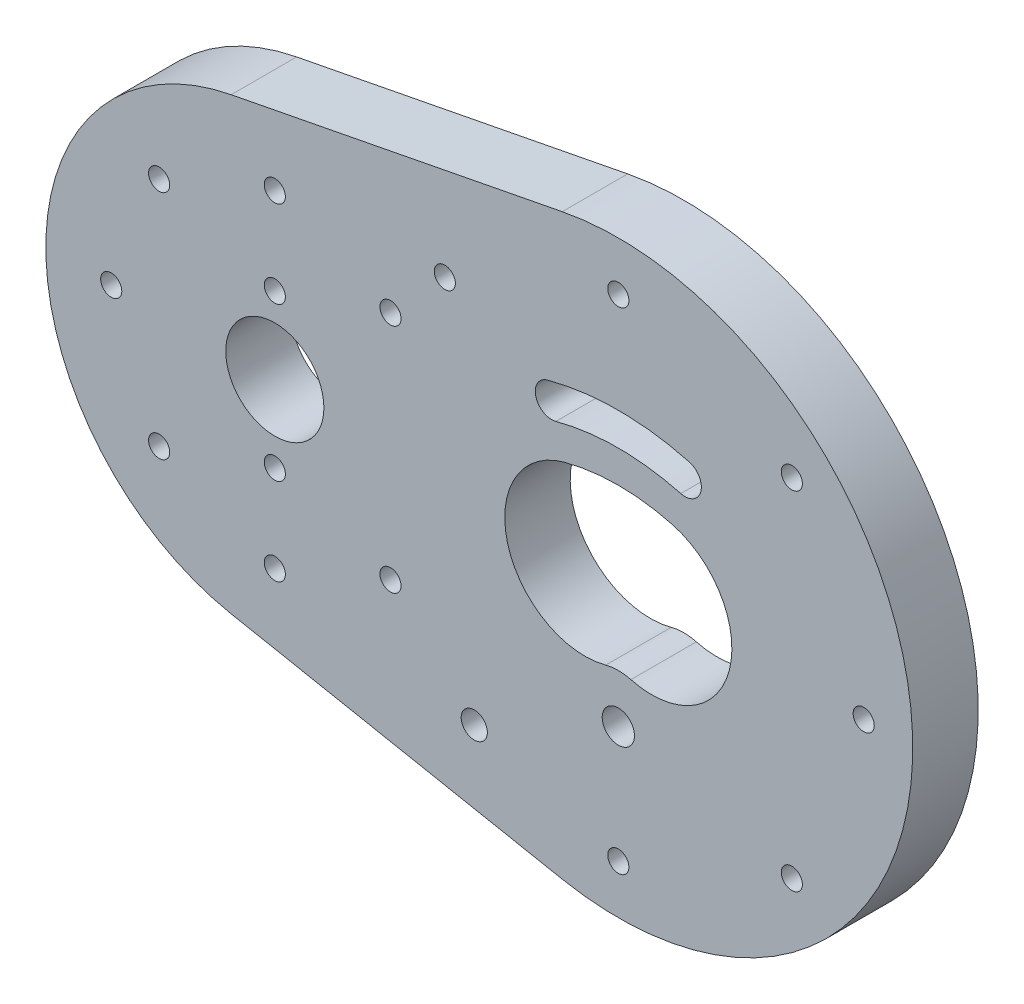
SolidWorks part; units mm, degrees
ref_plane "Front Plane" through (0, 0, 0) normal (0, 0, 1) x (1, 0, 0)
ref_plane "Top Plane" through (0, 0, 0) normal (0, 1, 0) x (1, 0, 0)
ref_plane "Right Plane" through (0, 0, 0) normal (1, 0, 0) x (0, 0, -1)
sketch "Sketch1" plane through (0, 0, 0) normal (0, 0, 1) x (1, 0, 0)
  line L0 (0, 0) -> (0, 36.4546) construction
  line L1 (0, 0) -> (-10.2847, 38.3829) construction
  line L2 (-33.3375, 12.5) -> (0, 12.5) construction
  line L4 (-91.5313, 56.95) -> (35.4687, 56.95)
  line L5 (-91.5313, 56.95) -> (-91.5313, -31.95)
  line L6 (-91.5313, -31.95) -> (35.4687, -31.95)
  line L7 (35.4687, 56.95) -> (35.4687, -31.95)
  line L8 (-91.5313, 56.95) -> (35.4687, -31.95) construction
  line L9 (-91.5313, -31.95) -> (35.4687, 56.95) construction
  arc A0 (5.2502, 19.5939) -> (1.2203, 4.5542) centre (3.2352, 12.0741) cw
  arc A1 (5.2502, 19.5939) -> (-5.2502, 19.5939) centre (0, 0) ccw
  circle A2 centre (0, 12.5) radius 12.5 construction
  circle A3 centre (0, 0) radius 1.5649
  arc A4 (10.8253, 6.25) -> (-10.8253, 6.25) centre (0, 0) ccw construction
  arc A5 (1.2203, 4.5542) -> (-1.2203, 4.5542) centre (0, 0) ccw
  arc A6 (-5.2502, 19.5939) -> (-1.2203, 4.5542) centre (-3.2352, 12.0741) ccw
  circle A7 centre (0, 25) radius 1.5875 construction
  arc A8 (6.8814, 25.6816) -> (-6.8814, 25.6816) centre (0, 0) ccw
  arc A9 (6.0596, 22.6147) -> (-6.0596, 22.6147) centre (0, 0) ccw
  circle A10 centre (0, 0) radius 25 construction
  arc A11 (-6.8814, 25.6816) -> (-6.0596, 22.6147) centre (-6.4705, 24.1481) ccw
  arc A12 (6.8814, 25.6816) -> (6.0596, 22.6147) centre (6.4705, 24.1481) cw
  circle A13 centre (-33.3375, 12.5) radius 4.7625
  circle A14 centre (-33.3375, 12.5) radius 25.4 construction
  point P0 (0, 0)
  point P18 (-28.0313, 12.5)
  dimension "D4" = 25
  dimension "D6" = 50.8
  dimension "D2" = 3.175
  dimension "D3" = 9.525
  dimension "D9" = 7.7851
  dimension "D1" = 15
  dimension "D5" = 33.3375
  dimension "D7" = 88.9
  dimension "D8" = 127
extrude "Boss-Extrude1" add sketch "Sketch1" along normal blind 6.35
sketch "Sketch2" plane through (0, 0, 6.35) normal (0, 0, 1) x (1, 0, 0)
  line L0 (-33.3375, 12.5) -> (43.934, 12.5) construction
  line L1 (0, 0) -> (0, 70.9306) construction
  line L2 (-37.5708, 34.3181) -> (-5.4429, 40.5518)
  line L3 (-37.5708, -9.3181) -> (-5.4429, -15.5518)
  line L5 (-107.0175, 80.3674) -> (70.5021, 80.3674)
  line L6 (-107.0175, 80.3674) -> (-107.0175, -46.3508)
  line L7 (-107.0175, -46.3508) -> (70.5021, -46.3508)
  line L8 (70.5021, 80.3674) -> (70.5021, -46.3508)
  arc A0 (-5.4429, -15.5518) -> (-5.4429, 40.5518) centre (0, 12.5) ccw
  arc A1 (-37.5708, 34.3181) -> (-37.5708, -9.3181) centre (-33.3375, 12.5) ccw
  dimension "D1" = 57.15
  dimension "D2" = 44.45
extrude "Cut-Extrude1" cut sketch "Sketch2" against normal through all
sketch "Sketch4" plane through (0, 0, 6.35) normal (0, 0, 1) x (1, 0, 0)
  line L0 (-33.3375, 12.5) -> (35.849, 12.5) construction
  line L1 (0, 0) -> (0, 48.1146) construction
  circle A0 centre (-33.3375, 12.5) radius 15.875 construction
  circle A1 centre (0, 12.5) radius 23.8125 construction
  circle A2 centre (-33.3375, 28.375) radius 0.635
  circle A3 centre (0, 36.3125) radius 0.635
  circle A4 centre (-22.1122, 23.7253) radius 0.635
  circle A5 centre (-17.4625, 12.5) radius 0.635 [skipped]
  circle A6 centre (-13.9821, -6.8554) radius 1.27
  circle A7 centre (-22.1122, 1.2747) radius 0.635
  circle A8 centre (-33.3375, -3.375) radius 0.635
  circle A9 centre (-44.5628, 1.2747) radius 0.635
  circle A10 centre (-49.2125, 12.5) radius 0.635
  circle A11 centre (16.838, 29.338) radius 0.635
  circle A12 centre (23.8125, 12.5) radius 0.635
  circle A13 centre (16.838, -4.338) radius 0.635
  circle A14 centre (0, -11.3125) radius 0.635
  circle A15 centre (-44.5628, 23.7253) radius 0.635
  circle A16 centre (-23.8125, 12.5) radius 0.635 [skipped]
  circle A17 centre (-16.838, 29.338) radius 0.635
  circle A18 centre (-16.838, -4.338) radius 0.635 [skipped]
  dimension "D1" = 47.625
  dimension "D2" = 31.75
  dimension "D3" = 1.27
  dimension "D4" = 1.27
  dimension "D6" = 8
  dimension "D5" = 8
extrude "Cut-Extrude2" cut sketch "Sketch4" against normal through all
sketch "Sketch5" plane through (0, 0, 6.35) normal (0, 0, 1) x (1, 0, 0)
  circle A0 centre (-33.3375, 12.5) radius 7.4422 construction
  circle A1 centre (-33.3375, 19.9422) radius 0.635
  circle A2 centre (-33.3375, 5.0578) radius 0.635
  dimension "D1" = 14.8844
  dimension "D2" = 1.27
  dimension "D3" = 1.27
extrude "Cut-Extrude3" cut sketch "Sketch5" against normal through all
hole_wizard "M2.5x0.45 Tapped Hole2" positions "3DSketch2" profile "Sketch6" tap size "M2.5x0.45" standard "Ansi Metric"
sketch3d "3DSketch2"
  line L0 (-44.5628, 23.7253, 0) -> (-44.5628, 23.7253, 6.35) construction
  line L1 (-49.2125, 12.5, 0) -> (-49.2125, 12.5, 6.35) construction
  line L2 (-44.5628, 1.2747, 0) -> (-44.5628, 1.2747, 6.35) construction
  line L3 (-33.3375, -3.375, 0) -> (-33.3375, -3.375, 6.35) construction
  line L4 (-22.1122, 1.2747, 0) -> (-22.1122, 1.2747, 6.35) construction
  line L5 (-22.1122, 23.7253, 0) -> (-22.1122, 23.7253, 6.35) construction
  line L6 (-33.3375, 28.375, 0) -> (-33.3375, 28.375, 6.35) construction
  line L7 (-16.838, 29.338, 0) -> (-16.838, 29.338, 6.35) construction
  line L8 (16.838, 29.338, 0) -> (16.838, 29.338, 6.35) construction
  line L9 (23.8125, 12.5, 0) -> (23.8125, 12.5, 6.35) construction
  line L10 (16.838, -4.338, 0) -> (16.838, -4.338, 6.35) construction
  line L11 (0, -11.3125, 0) -> (0, -11.3125, 6.35) construction
  line L12 (0, 36.3125, 0) -> (0, 36.3125, 6.35) construction
  line L13 (-33.3375, 19.9422, 0) -> (-33.3375, 19.9422, 6.35) construction
  line L14 (-33.3375, 5.0578, 0) -> (-33.3375, 5.0578, 6.35) construction
  point P0 (-44.5628, 23.7253, 6.35)
  point P4 (-49.2125, 12.5, 6.35)
  point P8 (-44.5628, 1.2747, 6.35)
  point P12 (-33.3375, -3.375, 6.35)
  point P16 (-22.1122, 1.2747, 6.35)
  point P20 (-22.1122, 23.7253, 6.35)
  point P24 (-33.3375, 28.375, 6.35)
  point P28 (-16.838, 29.338, 6.35)
  point P37 (16.838, 29.338, 6.35)
  point P41 (23.8125, 12.5, 6.35)
  point P45 (16.838, -4.338, 6.35)
  point P49 (0, -11.3125, 6.35)
  point P55 (0, 36.3125, 6.35)
  point P60 (-33.3375, 19.9422, 6.35)
  point P64 (-33.3375, 5.0578, 6.35)
sketch "Sketch6" plane through (-44.5628, 23.7253, 6.35) normal (1, 0, 0) x (0, -1, 0)
  line L0 (0, 0) -> (0, 7.9819)
  line L1 (0, 7.9819) -> (1.025, 7.366)
  line L2 (1.025, 7.366) -> (1.025, 0)
  line L5 (1.025, 0) -> (0, 0)
  line L10 (0, 7.9819) -> (-1.025, 7.366) construction
  line L11 (0, -6.35) -> (0, 107.95) construction
  dimension "Tap Drill Dia." = 2.05
  dimension "Tap Drill Depth" = 7.366
  dimension "Drill Angle" = 118
cosmetic thread "Hole Thread1" parameters "D1"=2.54, "D2"=2.5
cosmetic thread "Hole Thread2" parameters "D1"=2.54, "D2"=2.5
cosmetic thread "Hole Thread3" parameters "D1"=2.54, "D2"=2.5
cosmetic thread "Hole Thread4" parameters "D1"=2.54, "D2"=2.5
cosmetic thread "Hole Thread6" parameters "D1"=2.54, "D2"=2.5
cosmetic thread "Hole Thread7" parameters "D1"=2.54, "D2"=2.5
cosmetic thread "Hole Thread8" parameters "D1"=2.54, "D2"=2.5
cosmetic thread "Hole Thread9" parameters "D1"=2.54, "D2"=2.5
cosmetic thread "Hole Thread10" parameters "D1"=2.54, "D2"=2.5
cosmetic thread "Hole Thread11" parameters "D1"=2.54, "D2"=2.5
cosmetic thread "Hole Thread12" parameters "D1"=2.54, "D2"=2.5
cosmetic thread "Hole Thread13" parameters "D1"=2.54, "D2"=2.5
cosmetic thread "Hole Thread14" parameters "D1"=2.54, "D2"=2.5
cosmetic thread "Hole Thread15" parameters "D1"=2.54, "D2"=2.5
cosmetic thread "Hole Thread16" parameters "D1"=2.54, "D2"=2.5
